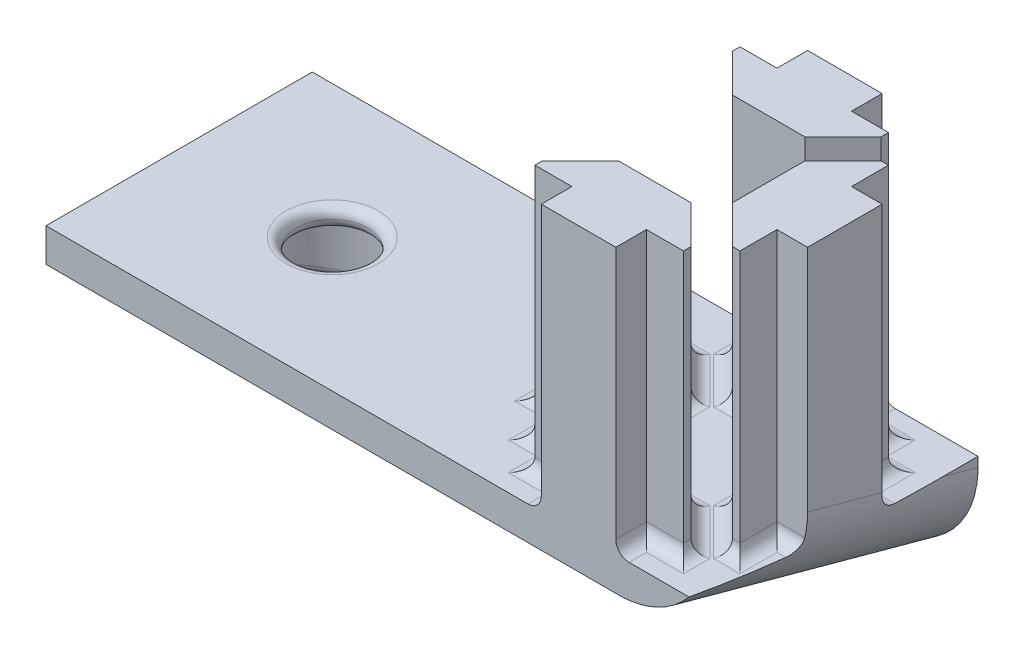
SolidWorks part; units mm, degrees
ref_plane "Front Plane" through (0, 0, 0) normal (0, 0, 1) x (1, 0, 0)
ref_plane "Top Plane" through (0, 0, 0) normal (0, 1, 0) x (1, 0, 0)
ref_plane "Right Plane" through (0, 0, 0) normal (1, 0, 0) x (0, 0, -1)
sketch "Sketch1" plane through (0, 0, 0) normal (0, 1, 0) x (1, 0, 0)
  line L20 (0, 0) -> (50000, 0) construction
  line L21 (-10, -2.8) -> (-10, 49997.2) construction
  line L22 (-10, -2.8) -> (-10, 2.8)
  line L23 (-7.1356, 5.58) -> (-4.28, 2.7244)
  line L24 (-7.7, 5.58) -> (-7.1356, 5.58)
  line L25 (-10, -2.8) -> (-7.7, -2.8)
  line L26 (-4.28, -2.7244) -> (-4.28, 2.7244)
  line L27 (-7.1356, -5.58) -> (-4.28, -2.7244)
  line L28 (-7.7, -5.58) -> (-7.1356, -5.58)
  line L29 (-7.7, -2.8) -> (-7.7, -5.58)
  line L30 (-7.7, 2.8) -> (-7.7, 5.58)
  line L31 (-10, 2.8) -> (-7.7, 2.8)
  line L32 (0, 0) -> (0, -50000) construction
  line L33 (10, 2.8) -> (7.7, 2.8)
  line L34 (7.7, 2.8) -> (7.7, 5.58)
  line L35 (7.7, -2.8) -> (7.7, -5.58)
  line L36 (7.7, -5.58) -> (7.1356, -5.58)
  line L37 (7.1356, -5.58) -> (4.28, -2.7244)
  line L38 (4.28, -2.7244) -> (4.28, 2.7244)
  line L39 (10, -2.8) -> (7.7, -2.8)
  line L40 (7.7, 5.58) -> (7.1356, 5.58)
  line L41 (7.1356, 5.58) -> (4.28, 2.7244)
  line L42 (10, -2.8) -> (10, 2.8)
  line L43 (0, 0) -> (35355.3391, -35355.3391) construction
  line L44 (0, 0) -> (0, -50000) construction
  line L45 (2.8, -10) -> (-2.8, -10)
  line L46 (-5.58, -7.1356) -> (-2.7244, -4.28)
  line L47 (-5.58, -7.7) -> (-5.58, -7.1356)
  line L48 (2.8, -10) -> (2.8, -7.7)
  line L49 (2.7244, -4.28) -> (-2.7244, -4.28)
  line L50 (5.58, -7.1356) -> (2.7244, -4.28)
  line L51 (5.58, -7.7) -> (5.58, -7.1356)
  line L52 (2.8, -7.7) -> (5.58, -7.7)
  line L53 (-2.8, -7.7) -> (-5.58, -7.7)
  line L54 (-2.8, -10) -> (-2.8, -7.7)
  line L55 (-2.8, 10) -> (-2.8, 7.7)
  line L56 (-2.8, 7.7) -> (-5.58, 7.7)
  line L57 (2.8, 7.7) -> (5.58, 7.7)
  line L58 (5.58, 7.7) -> (5.58, 7.1356)
  line L59 (5.58, 7.1356) -> (2.7244, 4.28)
  line L60 (2.7244, 4.28) -> (-2.7244, 4.28)
  line L61 (2.8, 10) -> (2.8, 7.7)
  line L62 (-5.58, 7.7) -> (-5.58, 7.1356)
  line L63 (-5.58, 7.1356) -> (-2.7244, 4.28)
  line L64 (2.8, 10) -> (-2.8, 10)
  point P12 (-4.28, 0)
  point P16 (-10, 0)
  point P28 (10, 0)
  point P29 (4.28, 0)
  point P44 (0, -4.28)
  point P45 (0, -10)
  point P56 (0, 10)
  point P57 (0, 4.28)
  dimension "D1" = 45
extrude "Boss-Extrude1" add sketch "Sketch1" along normal blind 20
sketch "Sketch2" plane through (0, 0, 0) normal (0, -1, 0) x (1, 0, 0)
  line L0 (-10, 10) -> (10, 10)
  line L1 (10, 10) -> (10, -10)
  line L2 (10, -10) -> (-10, -10)
  line L3 (-10, -10) -> (-10, 10)
  line L4 (2.8, -10) -> (-2.8, -10) construction
  line L5 (10, 2.8) -> (10, -2.8) construction
  line L6 (-2.8, 10) -> (2.8, 10) construction
  line L7 (-10, -2.8) -> (-10, 2.8) construction
extrude "Boss-Extrude2" add sketch "Sketch2" along normal blind 20
sketch "Sketch3" plane through (10, 0, 0) normal (1, 0, 0) x (0, 0, -1)
  line L2 (10.5967, -8.1372) -> (10.5967, -38.3455)
  line L3 (10.5967, -38.3455) -> (-10.4111, -38.3455)
  line L4 (-10.4111, -38.3455) -> (-10.4111, -2.4027)
  line L5 (10.5967, -8.1372) -> (-10.4111, -2.4027)
extrude "Cut-Extrude1" cut sketch "Sketch3" against normal through all
sketch "Sketch4" plane through (-10, 0, 0) normal (-1, 0, 0) x (0, 0, 1)
  line L0 (10, 0) -> (-10, 0)
  line L1 (-10, 0) -> (-10, -7.9743)
  line L2 (-10, -7.9743) -> (10, -2.5149)
  line L3 (10, -2.5149) -> (10, 0)
extrude "Boss-Extrude3" add sketch "Sketch4" along normal blind 30
fillet "Fillet1" radius 7 1 edges at (10, -5.2446, 0)
sketch "Sketch5" plane through (0, 0, 0) normal (0, 1, 0) x (1, 0, 0)
  line L0 (-40, -10) -> (-40, 10) construction
  circle A0 centre (-28.5, 0) radius 2.7
  dimension "D2" = 5.4
  dimension "D1" = 11.5
extrude "Cut-Extrude2" cut sketch "Sketch5" against normal up to next
ref_plane "Plane1" through (0, -1.5, 0) normal (0, 1, 0) x (1, 0, 0)
sketch "Sketch6" plane through (0, -1.5, 0) normal (0, 1, 0) x (1, 0, 0)
  circle A0 centre (-28.5, 0) radius 5
  dimension "D1" = 10
extrude "Cut-Extrude3" cut sketch "Sketch6" against normal up to next
fillet "Fillet5" radius 1 37 edges at (-4.28, 0, 0) (-5.7078, 0, 4.1522) (-7.4178, 0, 5.58) (-7.7, 0, 4.19) (-8.85, 0, 2.8) (-10, 0, 0) (-8.85, 0, -2.8) (-7.7, 0, -4.19) (-5.7078, 0, -4.1522) (-7.4178, 0, -5.58) (-2.8, 0, -8.85) (-4.19, 0, -7.7) (-5.58, 0, -7.4178) (-4.1522, 0, -5.7078) (0, 0, -4.28) (4.1522, 0, -5.7078) (5.58, 0, -7.4178) (4.19, 0, -7.7) (2.8, 0, -8.85) (8.7979, 0, -2.8) (7.7, 0, -4.19) (7.4178, 0, -5.58) (5.7078, 0, -4.1522) (4.28, 0, 0) (5.7078, 0, 4.1522) (7.4178, 0, 5.58) (8.5838, 0, 2.8) (7.7, 0, 4.19) (2.8, 0, 8.85) (4.19, 0, 7.7) (5.58, 0, 7.4178) (4.1522, 0, 5.7078) (0, 0, 4.28) (-4.1522, 0, 5.7078) (-5.58, 0, 7.4178) (-4.19, 0, 7.7) (-2.8, 0, 8.85)
fillet "Fillet6" radius 0.75 4 edges at (-28.5, 0, 2.7) (-28.5, -1.5, 2.7) (-28.5, -3.8798, 5) (-28.5, -1.5, 5)
sketch "Sketch7" plane through (0, 20, 0) normal (0, 1, 0) x (1, 0, 0)
  line L0 (-7.5556, 7.212) -> (-2.7669, 2.4234)
  line L1 (-2.7669, 2.4234) -> (-2.7669, -2.6971)
  line L2 (-2.7669, -2.6971) -> (-7.5556, -7.4858)
  line L3 (-7.5556, -7.4858) -> (-13.1028, -7.4858)
  line L4 (-13.1028, -7.4858) -> (-13.1028, 7.212)
  line L5 (-13.1028, 7.212) -> (-7.5556, 7.212)
extrude "Cut-Extrude4" cut sketch "Sketch7" against normal blind 10
